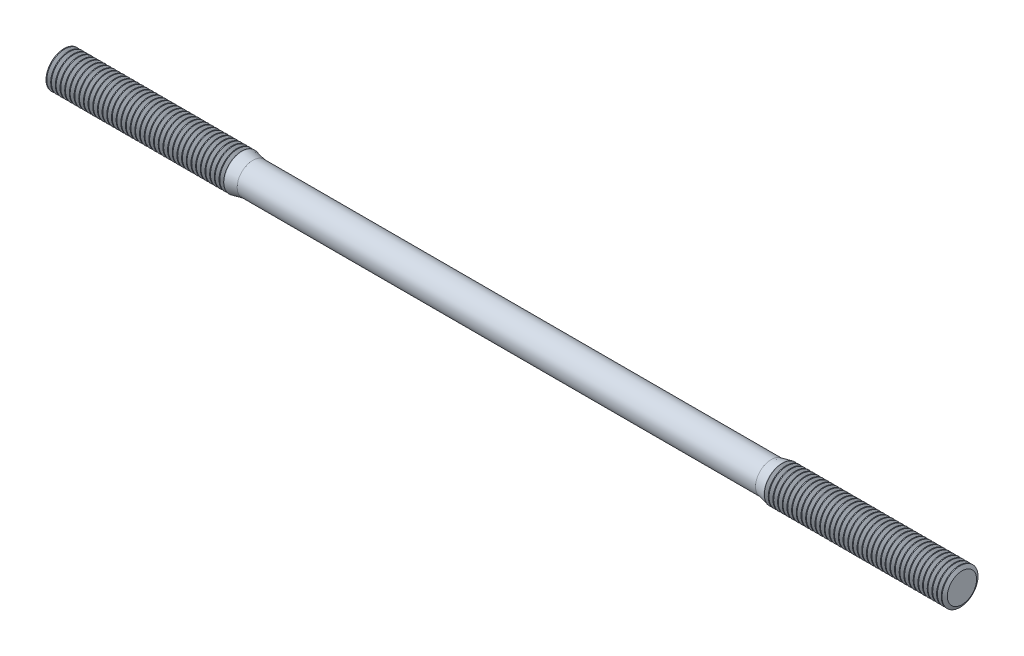
SolidWorks part; units mm, degrees
note: '?' marks a value the reader was unsure of.
material "AISI 304"
ref_plane "Front" through (0, 0, 0) normal (0, 0, 1) x (1, 0, 0)
ref_plane "Top" through (0, 0, 0) normal (0, 1, 0) x (1, 0, 0)
ref_plane "Right" through (0, 0, 0) normal (1, 0, 0) x (0, 0, -1)
other "Configuration Table"
sketch "Sketch2" plane through (0, 0, 0) normal (1, 0, 0) x (0, 0, -1)
  circle A0 centre (0, 0) radius 0.87
extrude "BaseBody" add sketch "Sketch2" along normal blind 50
sketch "Sketch3" plane through (0, 0, 0) normal (0, 0, 1) x (1, 0, 0)
  line L0 (-0.442, 0) -> (10.3933, 0) construction
  line L2 (50, 1) -> (50, 0)
  line L3 (50, 0.87) -> (0, 0.87) construction
  line L4 (50, 0) -> (39.4, 0)
  line L5 (39.4, 0) -> (39.4, 0.87)
  line L7 (39.4, 0.87) -> (40, 1)
  line L8 (40, 1) -> (50, 1)
  line L10 (50, -0.87) -> (50, 0.87) construction
  dimension "d" = 2
  dimension "b" = 10
revolve "BaseHead" add sketch "Sketch3" angle 360 about L0
cosmetic thread "ThreadCosmetic3" [suppressed] parameters "D2"=1.567
sketch "Sketch8" plane through (0, 0, 0) normal (0, 0, 1) x (1, 0, 0)
  line L0 (50, 0.8125) -> (50.1083, 1)
  line L1 (50.1083, 1) -> (50.1083, 1.2165)
  line L2 (50.1083, 1.2165) -> (49.8918, 1.2165)
  line L3 (49.8918, 1.2165) -> (49.8918, 1)
  line L4 (49.8918, 1) -> (50, 0.8125)
  line L5 (50, -1) -> (50, 1) construction
  line L6 (0, 0) -> (66.7307, 0) construction
  dimension "D2" = 0.2165
revolve "Cut-Revolve1" cut sketch "Sketch8" angle 360 about L6
pattern_linear "LPattern1" count 39 spacing 0.2598 along (-1, 0, 0) of "Cut-Revolve1"
sketch "Sketch6" plane through (0, 0, 0) normal (0, 0, 1) x (1, 0, 0)
  line L0 (-0.3771, 0) -> (10.1987, 0) construction
  line L2 (0, 0) -> (0, 1)
  line L3 (0, 1) -> (10, 1)
  line L4 (10, 1) -> (10.6, 0.87)
  line L5 (10.6, 0.87) -> (10.6, 0)
  line L6 (10.6, 0) -> (0, 0)
  dimension "D2" = 0.6
  dimension "D4" = 1.74
  dimension "d" = 2
  dimension "b" = 10
revolve "BaseEnd" add sketch "Sketch6" angle 360 about L0
cosmetic thread "ThreadCosmetic2" [suppressed] parameters "D2"=1.567
sketch "Sketch9" plane through (0, 0, 0) normal (0, 0, 1) x (1, 0, 0)
  line L0 (0, 0.8125) -> (0.1083, 1)
  line L1 (0.1083, 1) -> (0.1083, 1.2165)
  line L2 (0.1083, 1.2165) -> (-0.1082, 1.2165)
  line L3 (-0.1082, 1.2165) -> (-0.1082, 1)
  line L4 (-0.1082, 1) -> (0, 0.8125)
  line L5 (0, 0) -> (6.177, 0) construction
  line L6 (0, 1) -> (0, -1) construction
  dimension "D2" = 0.2165
revolve "Cut-Revolve2" cut sketch "Sketch9" angle 360 about L5
pattern_linear "LPattern2" count 39 spacing 0.2598 along (1, 0, 0) of "Cut-Revolve2"
sketch "Sketch7" plane through (0, 0, 0) normal (0, 0, 1) x (1, 0, 0)
  line L0 (-1.2267, 0) -> (25.8212, 0) construction
  line L2 (0, 0) -> (0, 1)
  line L3 (0, 1) -> (50, 1)
  line L4 (50, 1) -> (50, 0)
  line L5 (50, 0) -> (0, 0)
  dimension "D2" = 2
revolve "Revolve5" [suppressed] add sketch "Sketch7" angle 360 about L0
cosmetic thread "ThreadCosmetic1" [suppressed] parameters "D2"=1.567
sketch "Sketch10" [suppressed] plane through (0, 0, 0) normal (0, 0, 1) x (1, 0, 0)
  line L0 (65, 2.125) -> (65.2165, 2.5)
  line L1 (65.2165, 2.5) -> (65.2165, 2.933)
  line L2 (65.2165, 2.933) -> (64.7835, 2.933)
  line L3 (64.7835, 2.933) -> (64.7835, 2.5)
  line L4 (64.7835, 2.5) -> (65, 2.125)
  line L5 (65, -2.5) -> (65, 2.5) construction
  line L6 (0, 0) -> (67.1923, 0) construction
  dimension "D2" = 0.2165
revolve "Cut-Revolve3" [suppressed] cut sketch "Sketch10" angle 360 about L6
pattern_linear "LPattern3" [suppressed] count 193 spacing 0.2598 along (1, 0, 0)
ref_axis "Axis1" through (-66.49, 0, 0) along (1, 0, 0)?
equation "\"b@Sketch6\" = \"b@Sketch3\""
equation "\"d@Sketch6\" = \"d@Sketch3\""
equation "\"D2@Sketch6\" =\"x@Sketch3\""
equation "\"D4@Sketch6\" = \"ds@Sketch2\""
equation "\"D2@Sketch7\" = \"d@Sketch3\""
equation "\"D1@Sketch7\" =\"l@BaseBody\""
equation "\"D2@ThreadCosmetic2\" =\"D2@ThreadCosmetic1\""
equation "\"D2@ThreadCosmetic3\" =\"D2@ThreadCosmetic1\""
equation "\"D1@Sketch8\" = \"d@Sketch3\""
equation "\"D2@Sketch8\" =  ( \"d@Sketch3\" - \"D2@ThreadCosmetic3\" )  / 2"
equation "\"D3@LPattern1\" = \"D2@Sketch8\" * 1.2"
equation "\"D1@LPattern1\" = \"b@Sketch3\" / \"D3@LPattern1\" + 1"
equation "\"D1@Sketch9\" = \"d@Sketch6\""
equation "\"D2@Sketch9\" =  ( \"d@Sketch6\" - \"D2@ThreadCosmetic2\" )  / 2"
equation "\"D3@LPattern2\" = \"D2@Sketch9\" * 1.2"
equation "\"D1@LPattern2\" = \"b@Sketch6\" / \"D3@LPattern2\" + 1"
equation "\"D1@Sketch10\" = \"D2@Sketch7\""
equation "\"D2@Sketch10\" = (  \"D2@Sketch7\" - \"D2@ThreadCosmetic1\" )  / 2"
equation "\"D3@LPattern3\" = \"D2@Sketch10\" * 1.2"
equation "\"D1@LPattern3\" = \"D1@Sketch7\" / \"D3@LPattern3\" + 1"
